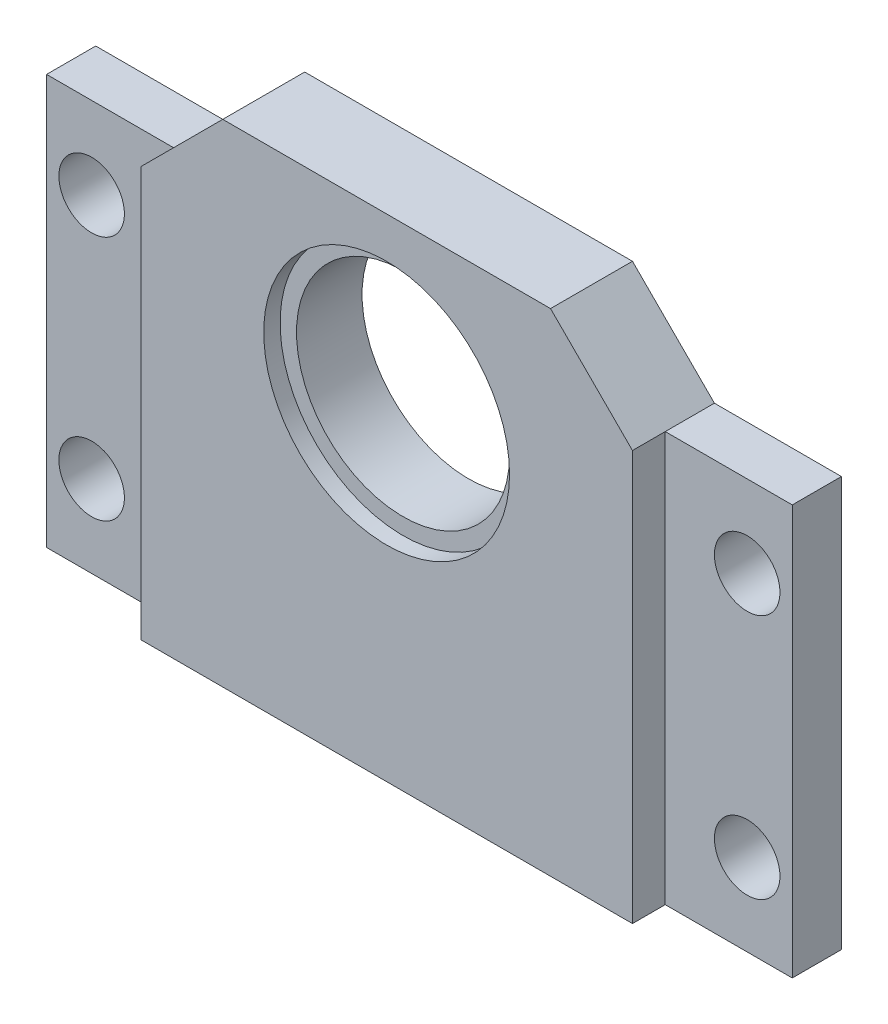
SolidWorks part; units mm, degrees
ref_plane "Plan de face" through (0, 0, 0) normal (0, 0, 1) x (1, 0, 0)
ref_plane "Plan de dessus" through (0, 0, 0) normal (0, 1, 0) x (1, 0, 0)
ref_plane "Plan de droite" through (0, 0, 0) normal (1, 0, 0) x (0, 0, -1)
sketch "Esquisse1" plane through (0, 0, 0) normal (0, 0, 1) x (1, 0, 0)
  line L1 (0, 0) -> (45.5, 0)
  line L2 (0, 0) -> (0, 25)
  line L3 (0, 25) -> (45.5, 25)
  line L4 (45.5, 0) -> (45.5, 25)
  dimension "D1" = 45.5
  dimension "D2" = 25
extrude "Boss.-Extru.1" add sketch "Esquisse1" along normal blind 3
sketch "Esquisse2" plane through (0, 0, 3) normal (0, 0, 1) x (1, 0, 0)
  line L0 (22.75, 0) -> (22.75, 25) construction
  line L1 (0, 0) -> (45.5, 0) construction
  line L2 (45.5, 25) -> (0, 25) construction
  line L3 (0, 12.5) -> (45.5, 12.5) construction
  line L4 (0, 25) -> (0, 0) construction
  line L5 (45.5, 0) -> (45.5, 25) construction
  circle A0 centre (2.75, 20) radius 2
  circle A1 centre (42.75, 20) radius 2
  circle A2 centre (42.75, 5) radius 2
  circle A3 centre (2.75, 5) radius 2
  dimension "D1" = 40
  dimension "D2" = 15
  dimension "D3" = 4
extrude "Enlèv. mat.-Extru.1" cut sketch "Esquisse2" against normal up to vertex (3 mm away) up to point (45.5, 25, 0)
sketch "Esquisse4" plane through (0, 0, 3) normal (0, 0, 1) x (1, 0, 0)
  line L0 (45.5, 25) -> (0, 25) construction
  line L1 (12.75, 25) -> (32.75, 25)
  line L2 (12.75, 25) -> (12.75, 30)
  line L3 (12.75, 30) -> (32.75, 30)
  line L4 (32.75, 25) -> (32.75, 30)
  line L5 (22.75, 25) -> (22.75, 0) construction
  line L6 (0, 0) -> (45.5, 0) construction
  dimension "D1" = 20
  dimension "D2" = 5
extrude "Boss.-Extru.2" add sketch "Esquisse4" against normal up to vertex (3 mm away) up to point (45.5, 25, 0)
sketch "Esquisse3" plane through (0, 0, 3) normal (0, 0, 1) x (1, 0, 0)
  line L0 (22.75, 0) -> (22.75, 31.6378) construction
  line L1 (0, 0) -> (45.5, 0) construction
  circle A0 centre (22.75, 20) radius 6.5
  dimension "D1" = 13
  dimension "D2" = 20
extrude "Enlèv. mat.-Extru.2" cut sketch "Esquisse3" against normal through all
chamfer "Chanfrein1" distance 5 angle 45 2 edges
sketch "Esquisse5" plane through (0, 0, 3) normal (0, 0, 1) x (1, 0, 0)
  line L0 (0, 0) -> (45.5, 0) construction
  line L1 (32.75, 30) -> (12.75, 30)
  line L2 (32.75, 30) -> (37.75, 25)
  line L3 (7.75, 0) -> (37.75, 0)
  line L4 (37.75, 25) -> (37.75, 0)
  line L5 (37.75, 25) -> (32.75, 30) construction
  line L6 (32.75, 30) -> (12.75, 30) construction
  line L7 (22.75, 20) -> (22.75, 0) construction
  line L8 (7.75, 25) -> (7.75, 0)
  line L9 (12.75, 30) -> (7.75, 25)
  circle A0 centre (22.75, 20) radius 6.5
  point P17 (22.75, 30)
  dimension "D1" = 13
  dimension "D2" = 30
extrude "Boss.-Extru.3" add sketch "Esquisse5" along normal blind 2
sketch "Esquisse6" plane through (0, 0, 5) normal (0, 0, 1) x (1, 0, 0)
  circle A0 centre (22.75, 20) radius 7.5
  dimension "D1" = 15
extrude "Enlèv. mat.-Extru.3" cut sketch "Esquisse6" against normal blind 1
